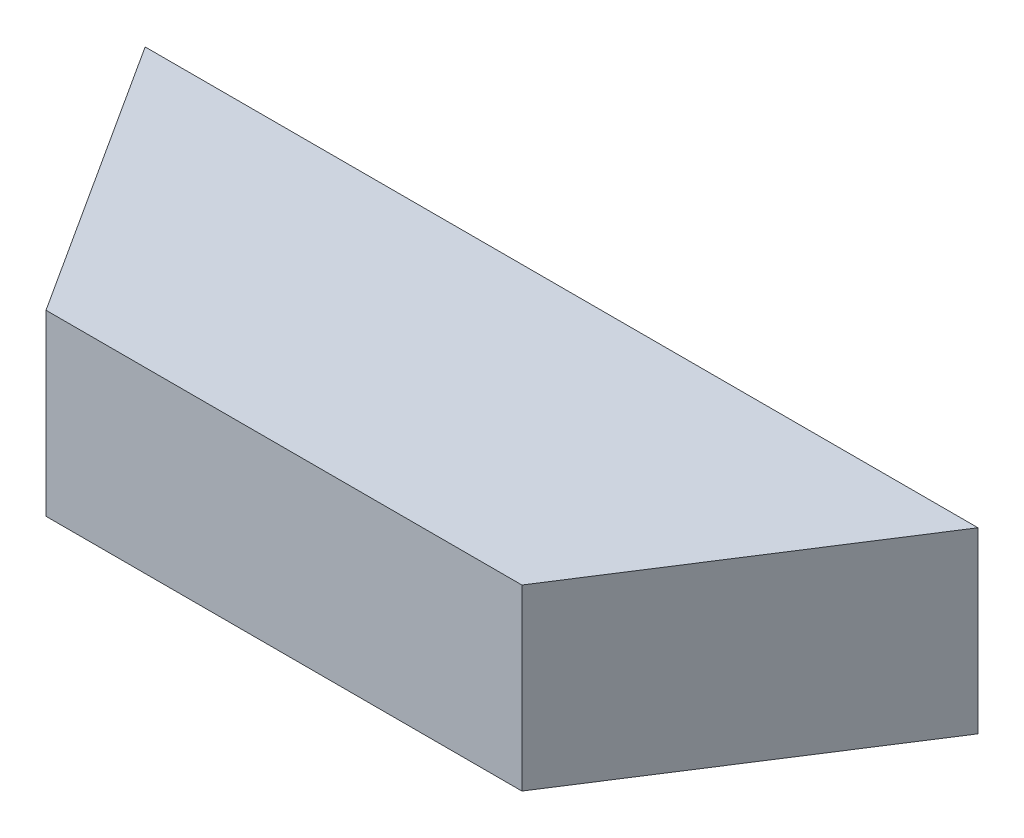
SolidWorks part; units mm, degrees
ref_plane "Front Plane" through (0, 0, 0) normal (0, 0, 1) x (1, 0, 0)
ref_plane "Top Plane" through (0, 0, 0) normal (0, 1, 0) x (1, 0, 0)
ref_plane "Right Plane" through (0, 0, 0) normal (1, 0, 0) x (0, 0, -1)
sketch "Sketch1" plane through (0, 0, 0) normal (0, 1, 0) x (1, 0, 0)
  line L0 (0, 0) -> (-152.4, 0)
  line L1 (-152.4, 0) -> (-209.55, 88.9)
  line L2 (-209.55, 88.9) -> (57.15, 88.9)
  line L3 (57.15, 88.9) -> (0, 0)
  point P3 (-76.2, 88.9)
  dimension "D1" = 152.4
  dimension "D2" = 266.7
  dimension "D3" = 88.9
  dimension "D4" = 76.2
extrude "Boss-Extrude1" add sketch "Sketch1" along normal blind 57.15
shell "Shell1" thickness 1.5875 removed face at (-76.2, 28.575, -88.9)
